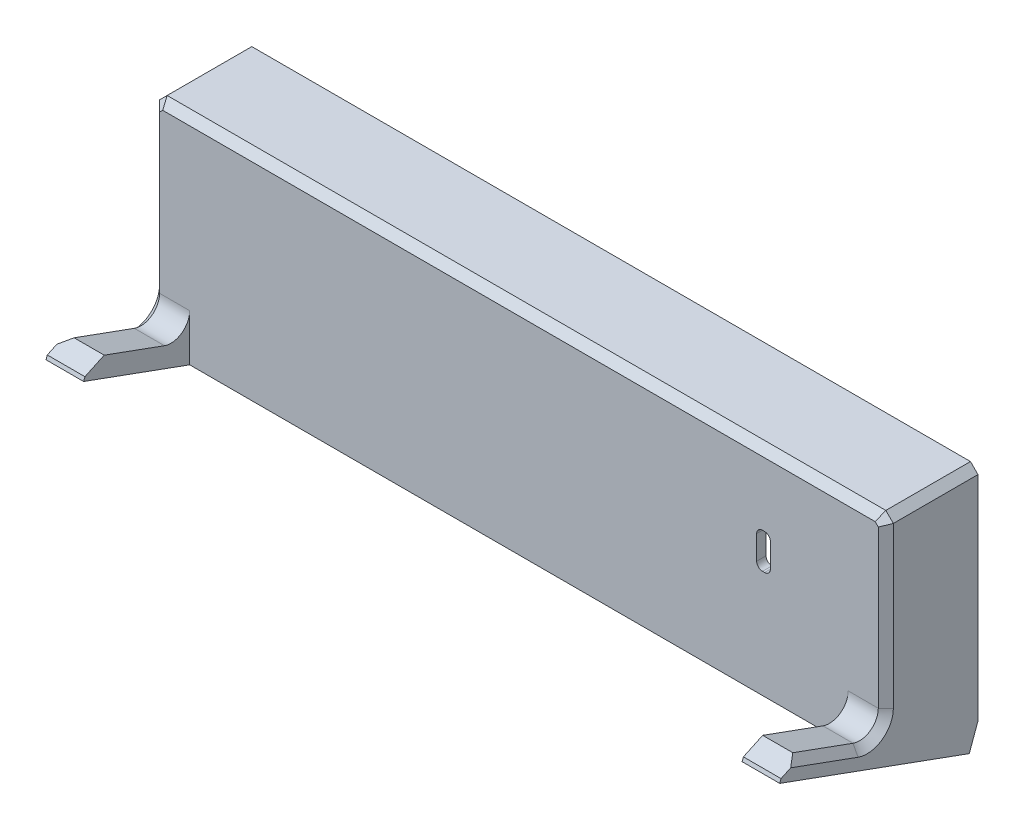
SolidWorks part; units mm, degrees
material "6061-T6 (SS)"
ref_plane "Front Plane" through (0, 0, 0) normal (0, 0, 1) x (1, 0, 0)
ref_plane "Top Plane" through (0, 0, 0) normal (0, 1, 0) x (1, 0, 0)
ref_plane "Right Plane" through (0, 0, 0) normal (1, 0, 0) x (0, 0, -1)
sketch "Croquis1" plane through (0, 0, 0) normal (0, 0, 1) x (1, 0, 0)
  line L0 (0, 27) -> (0, -27) construction
  line L1 (-95, 27) -> (95, 27) construction
  line L2 (95, -27) -> (-95, -27) construction
  line L3 (-95, 0) -> (95, 0) construction
  line L4 (-95, -27) -> (-95, 27) construction
  line L5 (95, 27) -> (95, -27) construction
  line L6 (-87.5, 23.5) -> (-87.5, 27.5)
  line L7 (-87.5, 27.5) -> (-95.5, 27.5)
  line L8 (-95.5, 27.5) -> (-95.5, 19.5)
  line L9 (-95.5, 19.5) -> (-91.5, 19.5)
  line L10 (-95.5, -19.5) -> (-91.5, -19.5)
  line L11 (-95.5, -27.5) -> (-95.5, -19.5)
  line L12 (-87.5, -27.5) -> (-95.5, -27.5)
  line L13 (-87.5, -23.5) -> (-87.5, -27.5)
  line L14 (87.5, -23.5) -> (87.5, -27.5)
  line L15 (87.5, -27.5) -> (95.5, -27.5)
  line L16 (95.5, -27.5) -> (95.5, -19.5)
  line L17 (95.5, -19.5) -> (91.5, -19.5)
  line L18 (95.5, 19.5) -> (91.5, 19.5)
  line L19 (95.5, 27.5) -> (95.5, 19.5)
  line L20 (87.5, 27.5) -> (95.5, 27.5)
  line L21 (87.5, 23.5) -> (87.5, 27.5)
  arc A0 (-91.5, 19.5) -> (-87.5, 23.5) centre (-91.5, 23.5) ccw
  arc A1 (-91.5, -19.5) -> (-87.5, -23.5) centre (-91.5, -23.5) cw
  arc A2 (91.5, -19.5) -> (87.5, -23.5) centre (91.5, -23.5) ccw
  arc A3 (91.5, 19.5) -> (87.5, 23.5) centre (91.5, 23.5) cw
  dimension "D1" = 8
extrude "Saliente-Extruir1" add sketch "Croquis1" along normal blind 9
sketch "Croquis2" plane through (0, 0, 9) normal (0, 0, 1) x (1, 0, 0)
  line L0 (-87.5, 27.5) -> (-95.5, 27.5) construction
  line L1 (-97.5, 27.5) -> (97.5, 27.5)
  line L2 (-97.5, 27.5) -> (-97.5, -27.5)
  line L3 (-97.5, -27.5) -> (97.5, -27.5)
  line L4 (97.5, 27.5) -> (97.5, -27.5)
  line L5 (-95.5, -27.5) -> (-87.5, -27.5) construction
  line L6 (0, 0) -> (0, 27.5) construction
  line L7 (95, 27) -> (95, -27) construction
  dimension "D1" = 2.5
extrude "Saliente-Extruir2" add sketch "Croquis2" along normal blind 2.5
sketch "Croquis3" plane through (0, 0, 11.5) normal (0, 0, 1) x (1, 0, 0)
  line L0 (65.2868, 1.3491) -> (64.7268, 1.3491) construction
  line L3 (66.5868, 2.6491) -> (66.5868, 5.8141) construction
  line L6 (66.5868, 5.8241) -> (66.5868, 8.9891) construction
  line L7 (65.2868, 10.2891) -> (64.7268, 10.2891) construction
  line L8 (66.8368, 2.6491) -> (66.8368, 5.8141)
  line L9 (65.2868, 1.0991) -> (64.7268, 1.0991)
  line L10 (63.1768, 2.6491) -> (63.1768, 8.9891)
  line L11 (65.2868, 10.5391) -> (64.7268, 10.5391)
  line L16 (63.4268, 2.6491) -> (63.4268, 8.9891) construction
  line L17 (65.2868, 1.3491) -> (64.7268, 1.3491) construction
  line L18 (66.5868, 2.6491) -> (66.5868, 5.8141) construction
  line L19 (66.5868, 5.8241) -> (66.5868, 8.9891) construction
  line L20 (65.2868, 10.2891) -> (64.7268, 10.2891) construction
  line L21 (63.4268, 2.6491) -> (63.4268, 8.9891) construction
  line L22 (66.8368, 5.8241) -> (66.8368, 8.9891)
  line L23 (66.8368, 5.8141) -> (66.8368, 5.8241)
  spline S0 degree 3 poles (63.4268, 2.6491) (63.4268, 1.8876) (63.9652, 1.3491) (64.7268, 1.3491) knots 0 0 0 0 1 1 1 1 weights 1 0.804738 0.804738 1 construction
  spline S1 degree 3 poles (65.2868, 1.3491) (66.0483, 1.3491) (66.5868, 1.8876) (66.5868, 2.6491) knots 0 0 0 0 1 1 1 1 weights 1 0.804738 0.804738 1 construction
  spline S2 degree 3 poles (66.5868, 8.9891) (66.5868, 9.7506) (66.0483, 10.2891) (65.2868, 10.2891) knots 0 0 0 0 1 1 1 1 weights 1 0.804738 0.804738 1 construction
  spline S3 degree 3 poles (63.4268, 8.9891) (63.4268, 9.7506) (63.9652, 10.2891) (64.7268, 10.2891) knots 0 0 0 0 1 1 1 1 weights 1 0.804738 0.804738 1 construction
  spline S4 degree 3 poles (63.4268, 2.6491) (63.4268, 1.8876) (63.9652, 1.3491) (64.7268, 1.3491) knots 0 0 0 0 1 1 1 1 weights 1 0.804738 0.804738 1 construction
  spline S5 degree 3 poles (65.2868, 1.3491) (66.0483, 1.3491) (66.5868, 1.8876) (66.5868, 2.6491) knots 0 0 0 0 1 1 1 1 weights 1 0.804738 0.804738 1 construction
  spline S6 degree 3 poles (66.5868, 8.9891) (66.5868, 9.7506) (66.0483, 10.2891) (65.2868, 10.2891) knots 0 0 0 0 1 1 1 1 weights 1 0.804738 0.804738 1 construction
  spline S7 degree 3 poles (63.4268, 8.9891) (63.4268, 9.7506) (63.9652, 10.2891) (64.7268, 10.2891) knots 0 0 0 0 1 1 1 1 weights 1 0.804738 0.804738 1 construction
  spline S8 degree 1 poles (65.2868, 1.0991) (66.8368, 2.6491) knots 0 0 1 1 construction
  spline S9 degree 1 poles (63.1768, 2.6491) (64.7268, 1.0991) knots 0 0 1 1 construction
  spline S10 degree 1 poles (63.1768, 8.9891) (64.7268, 10.5391) knots 0 0 1 1 construction
  spline S11 degree 1 poles (66.8368, 8.9891) (65.2868, 10.5391) knots 0 0 1 1 construction
  spline S12 degree 3 poles (66.8368, 2.6491) (66.8368, 2.4555) (66.7702, 2.0769) (66.4169, 1.519) (65.859, 1.1657) (65.4804, 1.0991) (65.2868, 1.0991) knots 0 0 0 0 0.25 0.5 0.75 1 1 1 1
  spline S13 degree 3 poles (64.7268, 1.0991) (64.5331, 1.0991) (64.1545, 1.1657) (63.5966, 1.519) (63.2434, 2.0769) (63.1768, 2.4555) (63.1768, 2.6491) knots 0 0 0 0 0.25 0.5 0.75 1 1 1 1
  spline S14 degree 3 poles (63.1768, 8.9891) (63.1768, 9.1827) (63.2434, 9.5613) (63.5966, 10.1192) (64.1545, 10.4725) (64.5331, 10.5391) (64.7268, 10.5391) knots 0 0 0 0 0.25 0.5 0.75 1 1 1 1
  spline S15 degree 3 poles (65.2868, 10.5391) (65.4804, 10.5391) (65.859, 10.4725) (66.4169, 10.1192) (66.7702, 9.5613) (66.8368, 9.1827) (66.8368, 8.9891) knots 0 0 0 0 0.25 0.5 0.75 1 1 1 1
  dimension "D1" = 0.25
extrude "Cortar-Extruir7" cut sketch "Croquis3" against normal blind 10 contours S14 L11 S15 L22 L23 L8 S12 L9 S13 L10
sketch "Croquis8" plane through (0, 0, 9) normal (0, 0, -1) x (-1, 0, 0)
  line L0 (-97.5, 0) -> (-96.2, 0) construction
  line L1 (-97.5, 27.5) -> (-95.5, 27.5)
  line L2 (-97.5, 27.5) -> (-97.5, -27.5)
  line L3 (-97.5, -27.5) -> (-95.5, -27.5)
  line L4 (-95.5, 27.5) -> (-95.5, 17.5)
  line L5 (-95.5, 17.5) -> (-96.2, 17.5)
  line L7 (-95.5, -17.5) -> (-96.2, -17.5)
  line L8 (-96.2, 17.5) -> (-96.2, -17.5)
  line L9 (-95.5, -17.5) -> (-95.5, -27.5)
  dimension "D1" = 35
  dimension "D2" = 1.3
extrude "Saliente-Extruir3" add sketch "Croquis8" along normal up to surface (9 mm away) up to face at (91.3343, 23.3343, 0)
sketch "Croquis9" plane through (0, 0, 9) normal (0, 0, -1) x (-1, 0, 0)
  line L1 (95.5, 27.5) -> (97.5, 27.5)
  line L2 (95.5, 27.5) -> (95.5, -27.5)
  line L3 (95.5, -27.5) -> (97.5, -27.5)
  line L4 (97.5, 27.5) -> (97.5, -27.5)
extrude "Saliente-Extruir4" add sketch "Croquis9" along normal up to surface (9 mm away) up to face at (-91.3343, 23.3343, 0)
sketch "Croquis10" plane through (0, 0, 0) normal (1, 0, 0) x (0, 0, -1)
  line L0 (-11.5, -27.5) -> (-39.6908, -17.2394)
  line L1 (-39.6908, -17.2394) -> (-39.3488, -16.2997)
  line L2 (-34.2219, -13.909) -> (-11.5, -22.1791)
  line L3 (-11.5, -27.5) -> (-11.5, 27.5) construction
  line L4 (-11.5, -22.1791) -> (-11.5, -27.5)
  line L5 (-39.3488, -16.2997) -> (-34.2219, -13.909)
  point P4 (-37.9807, -12.5409)
  dimension "D1" = 70
  dimension "D2" = 5
  dimension "D3" = 30
extrude "Saliente-Extruir5" add sketch "Croquis10" against normal blind 10 from surface starting at face at (97.5, 0, 5.75)
sketch "Croquis11" plane through (97.5, 0, 0) normal (1, 0, 0) x (0, 0, -1)
  line L0 (-11.5, -27.5) -> (0, -31.6857)
  line L1 (0, -31.6857) -> (0, -27.5)
  line L2 (-39.6908, -17.2394) -> (-11.5, -27.5) construction
  line L3 (-11.5, -27.5) -> (0, -27.5)
extrude "Saliente-Extruir6" add sketch "Croquis11" against normal through all contours L0 L1 L3
hole_wizard "Taladro roscado M31" positions "Croquis6" profile "Croquis7" tap size "M3" standard "DIN"
sketch "Croquis6" plane through (0, 0, 0) normal (0, 0, -1) x (-1, 0, 0)
  point P0 (-91.5, 23.5)
  point P3 (-91.5, -23.5)
  point P6 (91.5, -23.5)
  point P9 (91.5, 23.5)
cosmetic thread "Rosca de taladro1" parameters "D1"=8, "D2"=3
cosmetic thread "Rosca de taladro2" parameters "D1"=8, "D2"=3
cosmetic thread "Rosca de taladro3" parameters "D1"=8, "D2"=3
cosmetic thread "Rosca de taladro4" parameters "D1"=8, "D2"=3
sketch "Croquis7" plane through (91.5, 23.5, 0) normal (1, 0, 0) x (0, 1, 0)
  line L0 (0, 0) -> (0, 8.7511)
  line L1 (0, 8.7511) -> (1.25, 8)
  line L2 (1.25, 8) -> (1.25, 0.275)
  line L3 (1.25, 0.275) -> (1.525, 0)
  line L5 (1.525, 0) -> (0, 0)
  line L6 (-1.25, 0.275) -> (-1.525, 0) construction
  line L10 (0, 8.7511) -> (-1.25, 8) construction
  line L11 (0, -6.35) -> (0, 107.95) construction
  dimension "Diámetro de perforador para roscar" = 2.5
  dimension "Profundidad de perforador para roscar" = 8
  dimension "Diámetro de avellanado cercano" = 3.05
  dimension "Ángulo de avellanado cercano" = 90
  dimension "Ángulo de perforador" = 118
sketch "Croquis12" plane through (-97.5, 0, 0) normal (-1, 0, 0) x (0, 0, 1)
  line L6 (11.5, -27.5) -> (39.6908, -17.2394)
  line L7 (39.6908, -17.2394) -> (39.3488, -16.2997)
  line L8 (39.3488, -16.2997) -> (34.2219, -13.909)
  line L9 (34.2219, -13.909) -> (11.5, -22.1791)
  line L11 (11.5, -22.1791) -> (11.5, -27.5)
  line L12 (11.5, -27.5) -> (39.6908, -17.2394)
  line L13 (39.6908, -17.2394) -> (39.3488, -16.2997)
  line L14 (39.3488, -16.2997) -> (34.2219, -13.909)
  line L15 (34.2219, -13.909) -> (11.5, -22.1791)
  line L17 (11.5, -22.1791) -> (11.5, -27.5)
  dimension "D1" = 0
extrude "Saliente-Extruir7" add sketch "Croquis12" against normal blind 10
sketch "Croquis13" plane through (0, 27.5, 0) normal (0, 1, 0) x (1, 0, 0)
  line L1 (97.5, -11.5) -> (-97.5, -11.5)
  line L2 (97.5, -11.5) -> (97.5, 0)
  line L3 (97.5, 0) -> (-97.5, 0)
  line L4 (-97.5, -11.5) -> (-97.5, 0)
extrude "Saliente-Extruir8" add sketch "Croquis13" along normal blind 2
fillet "Redondeo2" radius 2 10 edges at (-87.5, -27.5, 4.5) (-95.5, -19.5, 4.5) (-95.5, 19.5, 4.5) (-87.5, 27.5, 4.5) (87.5, -27.5, 4.5) (95.5, -19.5, 4.5) (96.2, -17.5, 4.5) (96.2, 17.5, 4.5) (95.5, 19.5, 4.5) (87.5, 27.5, 4.5)
fillet "Redondeo3" radius 5 2 edges at (-92.5, -22.1791, 11.5) (92.5, -22.1791, 11.5)
sketch "Croquis14" plane through (0, 0, 0) normal (0, 0, -1) x (-1, 0, 0)
  line L0 (-95, -27) -> (-95, 27) construction
  line L1 (-95.2, 27.2) -> (95.2, 27.2)
  line L2 (-95.2, 27.2) -> (-95.2, 18.5536)
  line L3 (-95.2, -27.2) -> (95.2, -27.2)
  line L4 (97.5, -31.6857) -> (97.5, 29.5)
  line L5 (97.5, 29.5) -> (-97.5, 29.5)
  line L6 (-97.5, 29.5) -> (-97.5, -31.6857)
  line L7 (-97.5, -31.6857) -> (97.5, -31.6857)
  line L8 (97.5, -31.6857) -> (97.5, 29.5)
  line L9 (97.5, 29.5) -> (-97.5, 29.5)
  line L10 (-97.5, 29.5) -> (-97.5, -31.6857)
  line L11 (-97.5, -31.6857) -> (97.5, -31.6857)
  line L12 (95.2, 27.2) -> (95.2, -27.2)
  line L13 (-95, 27) -> (95, 27) construction
  line L14 (95, 27) -> (95, -27) construction
  line L15 (95, -27) -> (-95, -27) construction
  line L16 (-96.2, -15.9801) -> (-96.2, 15.9801) construction
  line L17 (-96.2, -15.9801) -> (-96.2, 15.9801)
  line L18 (-95.2, -18.5536) -> (-95.2, -27.2)
  arc A0 (-95.5, 17.5) -> (-96.2, 15.9801) centre (-94.2, 15.9801) ccw construction
  arc A1 (-93.5, 19.5) -> (-95.5, 17.5) centre (-93.5, 17.5) ccw construction
  arc A2 (-95.5, -17.5) -> (-93.5, -19.5) centre (-93.5, -17.5) ccw construction
  arc A3 (-96.2, -15.9801) -> (-95.5, -17.5) centre (-94.2, -15.9801) ccw construction
  arc A4 (-95.5, 17.5) -> (-96.2, 15.9801) centre (-94.2, 15.9801) ccw
  arc A5 (-95.2, 18.5536) -> (-95.5, 17.5) centre (-93.5, 17.5) ccw
  arc A6 (-95.5, -17.5) -> (-95.2, -18.5536) centre (-93.5, -17.5) ccw
  arc A7 (-96.2, -15.9801) -> (-95.5, -17.5) centre (-94.2, -15.9801) ccw
  dimension "D2" = 0.2
  dimension "D3" = 0.2
  dimension "D4" = 0.2
  dimension "D5" = 0.2
  dimension "D1" = 0
extrude "Saliente-Extruir9" add sketch "Croquis14" along normal up to surface (13 mm away)
sketch "Croquis15" plane through (0, 0, -13) normal (0, 0, -1) x (-1, 0, 0)
  line L0 (-95.2, 27.2) -> (-93.7858, 25.7858) construction
  line L1 (95.2, 27.2) -> (-95.2, 27.2) construction
  line L2 (0, 0) -> (-76.9212, 0) construction
  line L3 (0, 0) -> (0, 43.715) construction
  line L4 (-95.2, -27.2) -> (-93.7858, -25.7858) construction
  line L5 (95.2, -27.2) -> (93.7858, -25.7858) construction
  line L6 (95.2, 27.2) -> (93.7858, 25.7858) construction
  circle A0 centre (-93.7858, 25.7858) radius 2
  circle A1 centre (-93.7858, -25.7858) radius 2
  circle A2 centre (93.7858, -25.7858) radius 2
  circle A3 centre (93.7858, 25.7858) radius 2
  dimension "D1" = 4
  dimension "D2" = 45
extrude "Cortar-Extruir8" cut sketch "Croquis15" against normal up to surface (13 mm away) up to face at (89.975, -23.5, 0)
fillet "Redondeo4" radius 2 8 edges at (-92.3716, 27.2, -6.5) (-95.2, 24.3716, -6.5) (-95.2, -24.3716, -6.5) (-92.3716, -27.2, -6.5) (92.3716, -27.2, -6.5) (95.2, -24.3716, -6.5) (95.2, 24.3716, -6.5) (92.3716, 27.2, -6.5)
sketch "Croquis16" plane through (-97.5, 0, 0) normal (-1, 0, 0) x (0, 0, 1)
  line L0 (0, -31.6857) -> (-13, -36.4173)
  line L1 (-13, -36.4173) -> (-13, -31.6857)
  line L2 (-13, -31.6857) -> (-13, 29.5) construction
  line L3 (39.6908, -17.2394) -> (0, -31.6857) construction
  line L4 (-13, -31.6857) -> (0, -31.6857)
extrude "Saliente-Extruir10" add sketch "Croquis16" against normal up to surface (195 mm away) contours L0 L1 L4 up to face at (97.5, -9.8157, 14.1387)
sketch "Croquis17" plane through (-97.5, 0, 0) normal (-1, 0, 0) x (0, 0, 1)
  line L0 (-13, -29.2) -> (-10.6804, -35.573)
  line L1 (-13, -36.4173) -> (-13, 29.5) construction
  line L2 (39.6908, -17.2394) -> (-13, -36.4173) construction
  line L3 (-10.6804, -35.573) -> (-13, -36.4173)
  line L4 (-13, -36.4173) -> (-13, -29.2)
  line L5 (-13, -27.2) -> (0, -27.2) construction
  dimension "D1" = 2
extrude "Cortar-Extruir9" cut sketch "Croquis17" against normal through all
chamfer "Chaflán2" distance 2 angle 45 2 edges at (-97.5, 29.5, -0.75) (97.5, 29.5, -0.75)
chamfer "Chaflán3" distance 2 angle 45 9 edges at (-97.5, -16.8229, 26.216) (97.5, -16.8229, 26.216) (-97.5, -19.1341, 13.6321) (97.5, -19.1341, 13.6321) (-97.5, 6.2308, 11.5) (-96.5, 28.5, 11.5) (0, 29.5, 11.5) (97.5, 6.2308, 11.5) (96.5, 28.5, 11.5)
sketch "Croquis18" plane through (0, 0, 9) normal (0, 0, -1) x (-1, 0, 0)
  line L12 (-85.5, -27.5) -> (85.5, -27.5)
  line L13 (87.5, -25.5) -> (87.5, -23.5)
  line L14 (91.5, -19.5) -> (93.5, -19.5)
  line L15 (95.5, -17.5) -> (95.5, 17.5)
  line L16 (93.5, 19.5) -> (91.5, 19.5)
  line L17 (87.5, 23.5) -> (87.5, 25.5)
  line L18 (85.5, 27.5) -> (-85.5, 27.5)
  line L19 (-87.5, 25.5) -> (-87.5, 23.5)
  line L20 (-91.5, 19.5) -> (-93.5, 19.5)
  line L21 (-96.2, 15.9801) -> (-96.2, -15.9801)
  line L22 (-93.5, -19.5) -> (-91.5, -19.5)
  line L23 (-87.5, -23.5) -> (-87.5, -25.5)
  line L24 (-85.5, -27.5) -> (85.5, -27.5)
  line L25 (87.5, -25.5) -> (87.5, -23.5)
  line L26 (91.5, -19.5) -> (93.5, -19.5)
  line L27 (95.5, -17.5) -> (95.5, 17.5)
  line L28 (93.5, 19.5) -> (91.5, 19.5)
  line L29 (87.5, 23.5) -> (87.5, 25.5)
  line L30 (85.5, 27.5) -> (-85.5, 27.5)
  line L31 (-87.5, 25.5) -> (-87.5, 23.5)
  line L32 (-91.5, 19.5) -> (-93.5, 19.5)
  line L33 (-96.2, 15.9801) -> (-96.2, -15.9801)
  line L34 (-93.5, -19.5) -> (-91.5, -19.5)
  line L35 (-87.5, -23.5) -> (-87.5, -25.5)
  arc A14 (85.5, -27.5) -> (87.5, -25.5) centre (85.5, -25.5) ccw
  arc A15 (91.5, -19.5) -> (87.5, -23.5) centre (91.5, -23.5) ccw
  arc A16 (93.5, -19.5) -> (95.5, -17.5) centre (93.5, -17.5) ccw
  arc A17 (95.5, 17.5) -> (93.5, 19.5) centre (93.5, 17.5) ccw
  arc A18 (87.5, 23.5) -> (91.5, 19.5) centre (91.5, 23.5) ccw
  arc A19 (87.5, 25.5) -> (85.5, 27.5) centre (85.5, 25.5) ccw
  arc A20 (-85.5, 27.5) -> (-87.5, 25.5) centre (-85.5, 25.5) ccw
  arc A21 (-91.5, 19.5) -> (-87.5, 23.5) centre (-91.5, 23.5) ccw
  arc A22 (-93.5, 19.5) -> (-95.5, 17.5) centre (-93.5, 17.5) ccw
  arc A23 (-95.5, 17.5) -> (-96.2, 15.9801) centre (-94.2, 15.9801) ccw
  arc A24 (-96.2, -15.9801) -> (-95.5, -17.5) centre (-94.2, -15.9801) ccw
  arc A25 (-95.5, -17.5) -> (-93.5, -19.5) centre (-93.5, -17.5) ccw
  arc A26 (-87.5, -23.5) -> (-91.5, -19.5) centre (-91.5, -23.5) ccw
  arc A27 (-87.5, -25.5) -> (-85.5, -27.5) centre (-85.5, -25.5) ccw
  arc A28 (85.5, -27.5) -> (87.5, -25.5) centre (85.5, -25.5) ccw
  arc A29 (91.5, -19.5) -> (87.5, -23.5) centre (91.5, -23.5) ccw
  arc A30 (93.5, -19.5) -> (95.5, -17.5) centre (93.5, -17.5) ccw
  arc A31 (95.5, 17.5) -> (93.5, 19.5) centre (93.5, 17.5) ccw
  arc A32 (87.5, 23.5) -> (91.5, 19.5) centre (91.5, 23.5) ccw
  arc A33 (87.5, 25.5) -> (85.5, 27.5) centre (85.5, 25.5) ccw
  arc A34 (-85.5, 27.5) -> (-87.5, 25.5) centre (-85.5, 25.5) ccw
  arc A35 (-91.5, 19.5) -> (-87.5, 23.5) centre (-91.5, 23.5) ccw
  arc A36 (-93.5, 19.5) -> (-95.5, 17.5) centre (-93.5, 17.5) ccw
  arc A37 (-95.5, 17.5) -> (-96.2, 15.9801) centre (-94.2, 15.9801) ccw
  arc A38 (-96.2, -15.9801) -> (-95.5, -17.5) centre (-94.2, -15.9801) ccw
  arc A39 (-95.5, -17.5) -> (-93.5, -19.5) centre (-93.5, -17.5) ccw
  arc A40 (-87.5, -23.5) -> (-91.5, -19.5) centre (-91.5, -23.5) ccw
  arc A41 (-87.5, -25.5) -> (-85.5, -27.5) centre (-85.5, -25.5) ccw
  dimension "D1" = 0
extrude "Cortar-Extruir10" cut sketch "Croquis18" along normal through all
sketch "Croquis19" plane through (0, -27.5, 0) normal (0, 1, 0) x (1, 0, 0)
  line L0 (-87.5, -11.5) -> (-87.5, -39.6908) construction
  line L1 (87.5, 24.0476) -> (-87.5, 24.0476)
  line L2 (87.5, 24.0476) -> (87.5, -36.728)
  line L3 (87.5, -36.728) -> (-87.5, -36.728)
  line L4 (-87.5, 24.0476) -> (-87.5, -36.728)
  line L5 (87.5, -39.6908) -> (87.5, -11.5) construction
extrude "Cortar-Extruir11" cut sketch "Croquis19" against normal blind 10 from offset 2 offset against normal yes
sketch "Croquis20" plane through (0, 0, 9) normal (0, 0, -1) x (-1, 0, 0)
  line L0 (-91.5, -19.5) -> (91.5, -19.5)
  line L12 (-85.5, -27.5) -> (85.5, -27.5)
  line L13 (87.5, -25.5) -> (87.5, -23.5)
  line L14 (91.5, -19.5) -> (93.5, -19.5)
  line L15 (95.5, -17.5) -> (95.5, 17.5)
  line L16 (93.5, 19.5) -> (91.5, 19.5)
  line L17 (87.5, 23.5) -> (87.5, 25.5)
  line L18 (85.5, 27.5) -> (-85.5, 27.5)
  line L19 (-87.5, 25.5) -> (-87.5, 23.5)
  line L20 (-91.5, 19.5) -> (-93.5, 19.5)
  line L21 (-96.2, 15.9801) -> (-96.2, -15.9801)
  line L22 (-93.5, -19.5) -> (-91.5, -19.5)
  line L23 (-87.5, -23.5) -> (-87.5, -25.5)
  line L24 (-85.5, -27.5) -> (85.5, -27.5)
  line L25 (87.5, -25.5) -> (87.5, -23.5)
  line L34 (-93.5, -19.5) -> (-91.5, -19.5)
  line L35 (-87.5, -23.5) -> (-87.5, -25.5)
  arc A14 (85.5, -27.5) -> (87.5, -25.5) centre (85.5, -25.5) ccw
  arc A15 (91.5, -19.5) -> (87.5, -23.5) centre (91.5, -23.5) ccw
  arc A16 (93.5, -19.5) -> (95.5, -17.5) centre (93.5, -17.5) ccw
  arc A17 (95.5, 17.5) -> (93.5, 19.5) centre (93.5, 17.5) ccw
  arc A18 (87.5, 23.5) -> (91.5, 19.5) centre (91.5, 23.5) ccw
  arc A19 (87.5, 25.5) -> (85.5, 27.5) centre (85.5, 25.5) ccw
  arc A20 (-85.5, 27.5) -> (-87.5, 25.5) centre (-85.5, 25.5) ccw
  arc A21 (-91.5, 19.5) -> (-87.5, 23.5) centre (-91.5, 23.5) ccw
  arc A22 (-93.5, 19.5) -> (-95.5, 17.5) centre (-93.5, 17.5) ccw
  arc A23 (-95.5, 17.5) -> (-96.2, 15.9801) centre (-94.2, 15.9801) ccw
  arc A24 (-96.2, -15.9801) -> (-95.5, -17.5) centre (-94.2, -15.9801) ccw
  arc A25 (-95.5, -17.5) -> (-93.5, -19.5) centre (-93.5, -17.5) ccw
  arc A26 (-87.5, -23.5) -> (-91.5, -19.5) centre (-91.5, -23.5) ccw
  arc A27 (-87.5, -25.5) -> (-85.5, -27.5) centre (-85.5, -25.5) ccw
  arc A28 (85.5, -27.5) -> (87.5, -25.5) centre (85.5, -25.5) ccw
  arc A29 (91.5, -19.5) -> (87.5, -23.5) centre (91.5, -23.5) ccw
  arc A38 (-96.2, -15.9801) -> (-95.5, -17.5) centre (-94.2, -15.9801) ccw
  arc A39 (-95.5, -17.5) -> (-93.5, -19.5) centre (-93.5, -17.5) ccw
  arc A40 (-87.5, -23.5) -> (-91.5, -19.5) centre (-91.5, -23.5) ccw
  arc A41 (-87.5, -25.5) -> (-85.5, -27.5) centre (-85.5, -25.5) ccw
  line M35 (-85.5, -27.5) -> (85.5, -27.5)
  arc M36 (85.5, -27.5) -> (87.5, -25.5) centre (85.5, -25.5) ccw
  line M37 (87.5, -25.5) -> (87.5, -23.5)
  arc M38 (87.5, -23.5) -> (91.5, -19.5) centre (91.5, -23.5) cw
  arc M58 (-91.5, -19.5) -> (-87.5, -23.5) centre (-91.5, -23.5) cw
  line M59 (-87.5, -23.5) -> (-87.5, -25.5)
  arc M60 (-87.5, -25.5) -> (-85.5, -27.5) centre (-85.5, -25.5) ccw
  dimension "D1" = 0
extrude "Saliente-Extruir11" [suppressed] add sketch "Croquis20" along normal blind 2 contours L0 M58 M59 M60 M35 M36 M37 M38
sketch "Croquis21" [suppressed] plane through (0, -27.9791, 10.1836) normal (0, -0.9397, 0.342) x (1, 0, 0)
  line L1 (97.5, -22.203) -> (-97.5, -22.203)
  line L2 (97.5, -22.203) -> (97.5, 31.4009)
  line L3 (97.5, 31.4009) -> (-97.5, 31.4009)
  line L4 (-97.5, -22.203) -> (-97.5, 31.4009)
